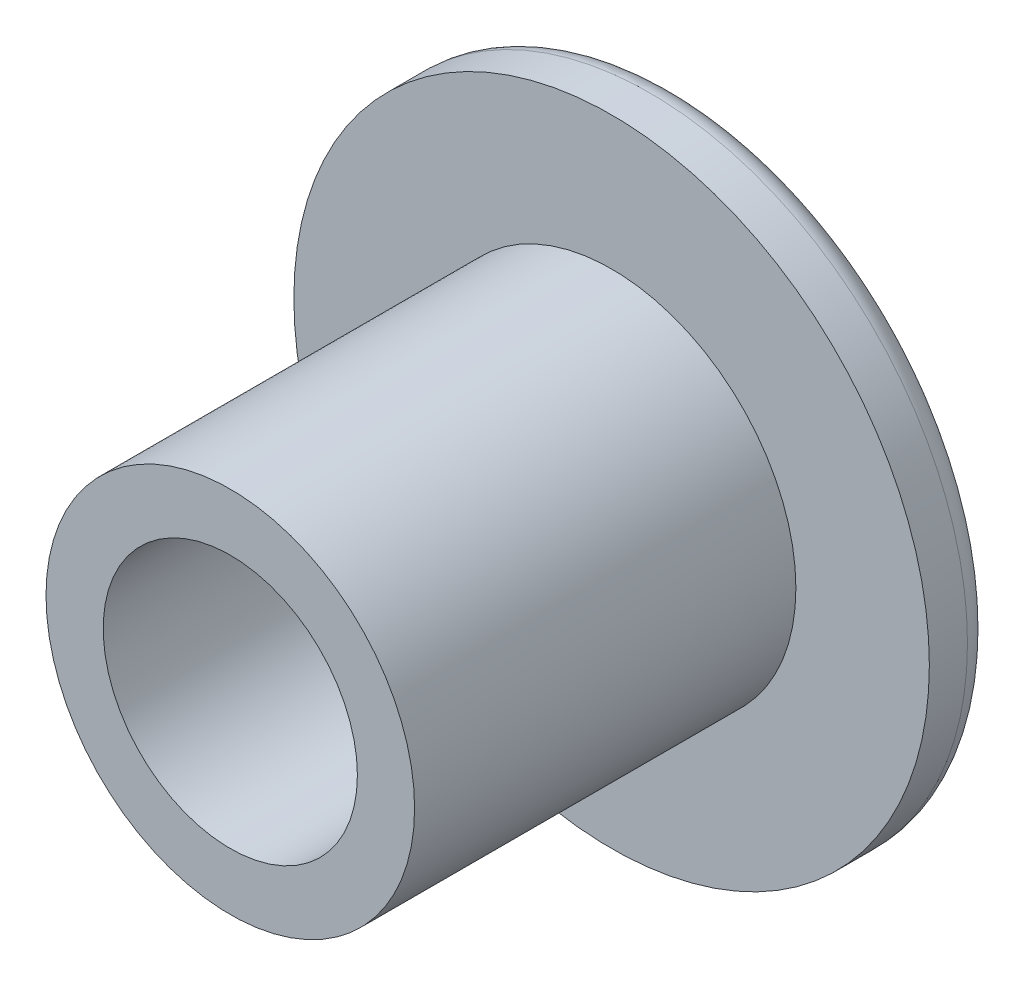
SolidWorks part; units mm, degrees
ref_plane "Front Plane" through (0, 0, 0) normal (0, 0, 1) x (1, 0, 0)
ref_plane "Top Plane" through (0, 0, 0) normal (0, 1, 0) x (1, 0, 0)
ref_plane "Right Plane" through (0, 0, 0) normal (1, 0, 0) x (0, 0, -1)
sketch "Sketch1" plane through (0, 0, 0) normal (0, 0, 1) x (1, 0, 0)
  circle A0 centre (0, 0) radius 5
  dimension "D1" = 10
extrude "Boss-Extrude1" add sketch "Sketch1" along normal blind 1 contours A0
sketch "Sketch2" plane through (0, 0, 1) normal (0, 0, 1) x (1, 0, 0)
  circle A0 centre (0, 0) radius 2.9
  dimension "D1" = 5.8
extrude "Boss-Extrude2" add sketch "Sketch2" along normal blind 6
sketch "Sketch3" plane through (0, 0, 7) normal (0, 0, 1) x (1, 0, 0)
  circle A0 centre (0, 0) radius 2
  dimension "D1" = 4
extrude "Cut-Extrude2" cut sketch "Sketch3" against normal through all both and the other way through all contours A0
fillet "Fillet1" radius 0.4 1 edges at (5, 0, 0)
fillet "Fillet2" radius 0.2 1 edges at (2, 0, 0)
